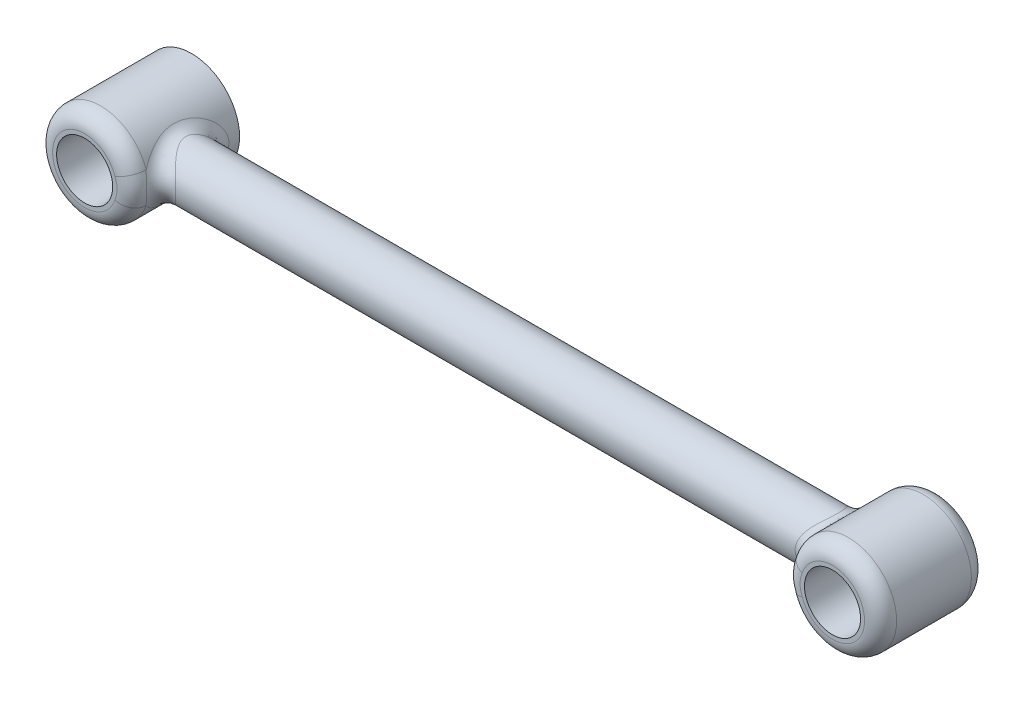
SolidWorks part; units mm, degrees
material "Plain Carbon Steel"
ref_plane "Front Plane" through (0, 0, 0) normal (0, 0, 1) x (1, 0, 0)
ref_plane "Top Plane" through (0, 0, 0) normal (0, 1, 0) x (1, 0, 0)
ref_plane "Right Plane" through (0, 0, 0) normal (1, 0, 0) x (0, 0, -1)
sketch "Sketch1" plane through (0, 0, 0) normal (0, 0, 1) x (1, 0, 0)
  line L0 (-60, 0) -> (60, 0)
  point P4 (0, 0)
  dimension "D1" = 120
sweep "Sweep1" add path "Sketch1" circular profile diameter 10 parameters "D3"=10
sketch "Sketch10" plane through (0, 0, 0) normal (0, 0, 1) x (1, 0, 0)
  line L0 (-70, 0) -> (70, 0) construction
  line L1 (0, 5) -> (0, -5) construction
  line L2 (60, 5) -> (-60, 5) construction
  line L3 (-60, -5) -> (60, -5) construction
  circle A1 centre (-70, 0) radius 9
  circle A2 centre (70, 0) radius 9
  circle A3 centre (-70, 0) radius 5.25
  circle A4 centre (70, 0) radius 5.25
  point P4 (0, 0)
  dimension "D2" = 18
  dimension "D3" = 10.5
  dimension "D1" = 140
extrude "Boss-Extrude1" add sketch "Sketch10" along normal mid plane 20 separate body contours A1 A3 | A2 A4 region at (-78.7454, 0, 0) region at (61.2546, 0, 0)
other "Move Face1" face at (60, 5, 0) face at (-60, 5, 0) offset 3 parameters "D1"=3
combine bodies "Combine1" operation type add bodies to combine 103 105 104
fillet "Fillet1" radius 3 2 edges at (62.5053, -4.9829, -0.4132) (-62.5053, -4.9829, 0.4132)
fillet "Fillet2" radius 3 3 edges at (79, 0, -10) (79, 0, 10) (-61, 0, 10)
sketch3d "3DSketch1"
  line L0 (70, 0, -10) -> (70, 0, 10) construction
  line L1 (70, 0, 10) -> (70, 0, -10) construction
  line L2 (70, 0, -12.0592) -> (70, 0, 3.1184) construction
  line L3 (70, 0, 1.9408) -> (70, 0, 17.1184) construction
